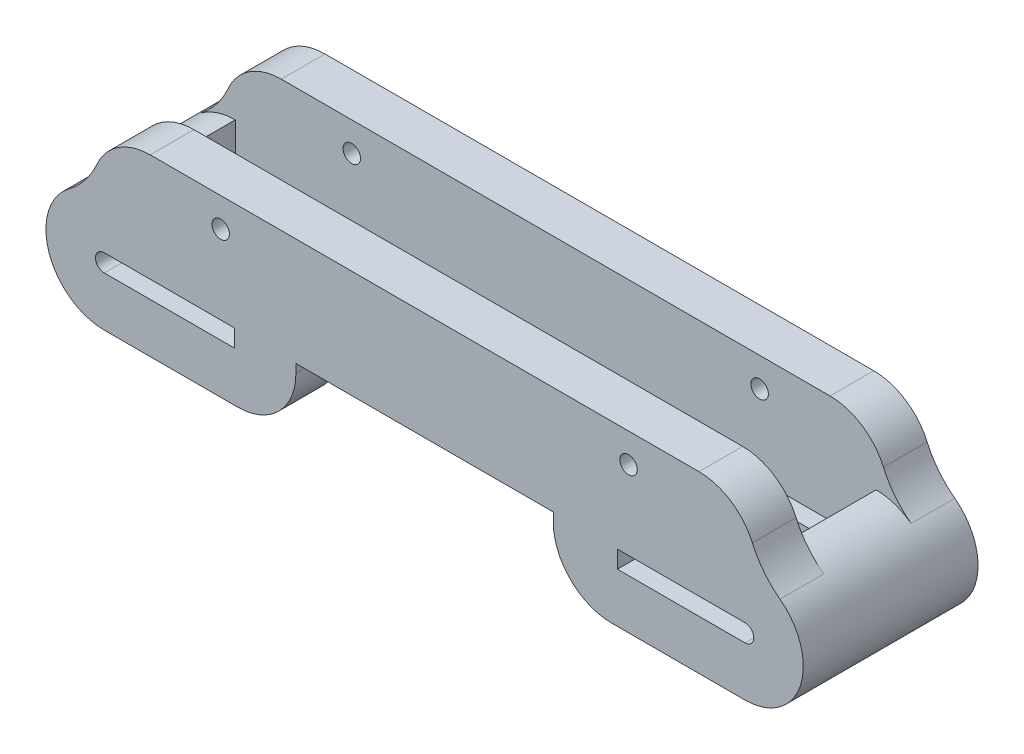
SolidWorks part; units mm, degrees
ref_plane "Plan de face" through (0, 0, 0) normal (0, 0, 1) x (1, 0, 0)
ref_plane "Plan de dessus" through (0, 0, 0) normal (0, 1, 0) x (1, 0, 0)
ref_plane "Plan de droite" through (0, 0, 0) normal (1, 0, 0) x (0, 0, -1)
sketch "Esquisse1" plane through (0, 0, 0) normal (0, 0, 1) x (1, 0, 0)
  line L0 (-55, 0) -> (55, 0) construction
  line L1 (-55, 10) -> (55, 10)
  line L2 (-55, -10) -> (55, -10)
  line L3 (-55, 0) -> (55, 0) construction
  line L4 (-55, 1.5) -> (55, 1.5)
  line L5 (-55, -1.5) -> (55, -1.5)
  arc A0 (-55, 10) -> (-55, -10) centre (-55, 0) ccw
  arc A1 (55, -10) -> (55, 10) centre (55, 0) ccw
  arc A2 (-55, 1.5) -> (-55, -1.5) centre (-55, 0) ccw
  arc A3 (55, -1.5) -> (55, 1.5) centre (55, 0) ccw
  point P2 (0, 0)
  point P10 (0, 0)
  dimension "D1" = 10
  dimension "D2" = 1.5
  dimension "D3" = 110
extrude "Boss.-Extru.1" add sketch "Esquisse1" along normal blind 30
sketch "Esquisse2" plane through (0, 10, 0) normal (0, 1, 0) x (1, 0, 0)
  line L0 (0, 0) -> (0, -30) construction
  line L1 (55, -30) -> (-55, -30) construction
  line L2 (-55, -30) -> (-55, 0) construction
  line L3 (-55, -7.5) -> (55, -7.5)
  line L4 (-55, -7.5) -> (-55, -22.5)
  line L5 (-55, -22.5) -> (55, -22.5)
  line L6 (55, -7.5) -> (55, -22.5)
  line L7 (-55, -7.5) -> (55, -22.5) construction
  line L8 (-55, -22.5) -> (55, -7.5) construction
  point P5 (0, -15)
  dimension "D1" = 15
extrude "Enlèv. mat.-Extru.1" cut sketch "Esquisse2" against normal blind 30
sketch "Esquisse3" plane through (0, 10, 0) normal (0, 1, 0) x (1, 0, 0)
  line L0 (-55, -22.5) -> (55, -22.5) construction
  line L1 (-22.095, -30) -> (22.095, -30)
  line L2 (-22.095, -30) -> (-22.095, -22.5)
  line L3 (-22.095, -22.5) -> (22.095, -22.5)
  line L4 (22.095, -30) -> (22.095, -22.5)
  line L5 (-22.095, -30) -> (22.095, -22.5) construction
  line L6 (-22.095, -22.5) -> (22.095, -30) construction
  line L7 (55, -30) -> (-55, -30) construction
  line L8 (-65, 0) -> (-65, -30) construction
  line L9 (-55, -7.5) -> (-55, -22.5) construction
  line L10 (55, -30) -> (55, -22.5) construction
  point P0 (0, -26.25)
  dimension "D1" = 44.19
extrude "Enlèv. mat.-Extru.2" cut sketch "Esquisse3" against normal blind 10 from offset 10 offset against normal yes
sketch "Esquisse4" plane through (0, -1.5, 0) normal (0, 1, 0) x (1, 0, 0)
  line L0 (-27.095, -22.5) -> (-27.095, -30)
  line L1 (27.095, -22.5) -> (27.095, -30)
  line L4 (-22.095, -30) -> (-22.095, -22.5)
  line L5 (-22.095, -22.5) -> (-55, -22.5)
  line L6 (-55, -22.5) -> (-55, -30)
  line L7 (-55, -30) -> (-22.095, -30)
  line L8 (-22.095, -30) -> (-22.095, -22.5)
  line L9 (-22.095, -22.5) -> (-27.095, -22.5)
  line L11 (-27.095, -30) -> (-22.095, -30)
  line L12 (22.095, -22.5) -> (22.095, -30)
  line L13 (22.095, -30) -> (55, -30)
  line L14 (55, -30) -> (55, -22.5)
  line L15 (55, -22.5) -> (22.095, -22.5)
  line L16 (22.095, -22.5) -> (22.095, -30)
  line L17 (22.095, -30) -> (27.095, -30)
  line L19 (27.095, -22.5) -> (22.095, -22.5)
  dimension "D3" = 5
  dimension "D4" = 5
  dimension "D1" = 0
  dimension "D2" = 0
extrude "Boss.-Extru.2" add sketch "Esquisse4" along normal blind 10
sketch "Esquisse5" plane through (27.095, 0, 0) normal (1, 0, 0) x (0, 0, -1)
  line L4 (-22.5, 1.5) -> (-30, 1.5)
  line L5 (-30, 1.5) -> (-30, -1.5)
  line L6 (-30, -1.5) -> (-22.5, -1.5)
  line L7 (-22.5, -1.5) -> (-22.5, 1.5)
  line L8 (-22.5, 1.5) -> (-30, 1.5)
  line L9 (-30, 1.5) -> (-30, -1.5)
  line L10 (-30, -1.5) -> (-22.5, -1.5)
  line L11 (-22.5, -1.5) -> (-22.5, 1.5)
  dimension "D1" = 0
extrude "Boss.-Extru.3" add sketch "Esquisse5" along normal blind 6
sketch "Esquisse6" plane through (-27.095, 0, 0) normal (-1, 0, 0) x (0, 0, 1)
  line L4 (30, 1.5) -> (22.5, 1.5)
  line L5 (22.5, 1.5) -> (22.5, -1.5)
  line L6 (22.5, -1.5) -> (30, -1.5)
  line L7 (30, -1.5) -> (30, 1.5)
  line L8 (30, 1.5) -> (22.5, 1.5)
  line L9 (22.5, 1.5) -> (22.5, -1.5)
  line L10 (22.5, -1.5) -> (30, -1.5)
  line L11 (30, -1.5) -> (30, 1.5)
  dimension "D1" = 0
extrude "Boss.-Extru.4" add sketch "Esquisse6" along normal blind 5.5
fillet "Congé1" radius 10 2 edges at (-22.095, -10, 26.25) (22.095, -10, 26.25)
sketch "Esquisse7" plane through (0, 10, 0) normal (0, 1, 0) x (1, 0, 0)
  line L4 (-55, 0) -> (-55, -7.5)
  line L5 (-55, -7.5) -> (55, -7.5)
  line L6 (55, -7.5) -> (55, 0)
  line L7 (55, 0) -> (-55, 0)
  line L8 (-55, 0) -> (-55, -7.5)
  line L9 (-55, -7.5) -> (55, -7.5)
  line L10 (55, -7.5) -> (55, 0)
  line L11 (55, 0) -> (-55, 0)
  line L12 (55, -30) -> (55, -22.5)
  line L13 (55, -22.5) -> (-55, -22.5)
  line L14 (-55, -22.5) -> (-55, -30)
  line L15 (-55, -30) -> (55, -30)
  line L16 (55, -30) -> (55, -22.5)
  line L17 (55, -22.5) -> (-55, -22.5)
  line L18 (-55, -22.5) -> (-55, -30)
  line L19 (-55, -30) -> (55, -30)
  dimension "D1" = 0
  dimension "D2" = 0
extrude "Boss.-Extru.5" add sketch "Esquisse7" along normal blind 10
sketch "Esquisse8" plane through (0, 0, 7.5) normal (0, 0, 1) x (1, 0, 0)
  line L7 (-55, 15) -> (55, 15) construction
  line L8 (-55, 20) -> (-55, 10) construction
  line L9 (55, 20) -> (55, 10) construction
  line L10 (0, 20) -> (0, -10) construction
  line L11 (55, -10) -> (-55, -10) construction
  line L12 (-55, 20) -> (55, 20) construction
  circle A0 centre (-35, 15) radius 1.5
  circle A1 centre (35, 15) radius 1.5
  point P11 (0, -10)
  point P14 (0, 20)
  dimension "D1" = 3
  dimension "D2" = 20
extrude "Enlèv. mat.-Extru.3" cut sketch "Esquisse8" against normal through all and the other way through all
fillet "Congé2" radius 15 1 edges at (-55, 10, 3.75) type face fillet first side face at (-57.5, 0, 15) second side face at (-55, 15, 3.75)
fillet "Congé3" radius 15 1 edges at (55, 10, 3.75) type face fillet first side face at (55, 15, 3.75) second side face at (57.5, 0, 15)
fillet "Congé4" radius 15 1 edges at (-55, 10, 26.25) type face fillet first side face at (-55, 15, 26.25) second side face at (-58.1832, 0.4805, 14.1667)
fillet "Congé5" radius 15 1 edges at (55, 10, 26.25) type face fillet first side face at (55, 15, 26.25) second side face at (58.1832, 0.4805, 14.1667)
fillet "Congé6" radius 10 4 edges at (55, 20, 26.25) (55, 20, 3.75) (-55, 20, 26.25) (-55, 20, 3.75)
